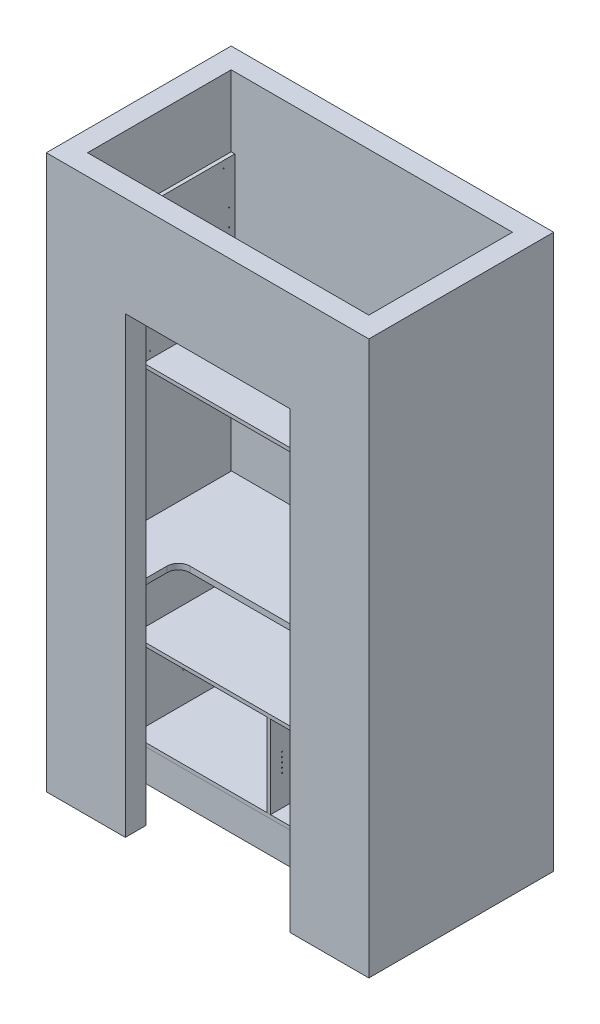
SolidWorks part; units mm, degrees
ref_plane "Front" through (0, 0, 0) normal (0, 0, 1) x (1, 0, 0)
ref_plane "Top" through (0, 0, 0) normal (0, 1, 0) x (1, 0, 0)
ref_plane "Right" through (0, 0, 0) normal (1, 0, 0) x (0, 0, -1)
sketch "Sketch1" plane through (0, 0, 0) normal (0, 1, 0) x (1, 0, 0)
  line L0 (-90, 90) -> (1318, 90)
  line L1 (0, 0) -> (1228, 0)
  line L2 (0, 0) -> (0, -627)
  line L3 (0, -627) -> (255, -627)
  line L4 (1228, 0) -> (1228, -627)
  line L5 (1318, 90) -> (1318, -717)
  line L6 (-90, -717) -> (255, -717)
  line L7 (-90, 90) -> (-90, -717)
  line L8 (255, -627) -> (255, -717)
  line L9 (973, -627) -> (973, -717)
  line L10 (973, -717) -> (1318, -717)
  line L11 (973, -627) -> (1228, -627)
  line L12 (-90, -717) -> (1318, -717) construction
  line L13 (255, -627) -> (973, -627)
  line L14 (0, -627) -> (1228, -627) construction
  line L15 (255, -717) -> (973, -717)
  dimension "D1" = 1228
  dimension "D2" = 627
  dimension "D4" = 255
  dimension "D5" = 255
  dimension "D3" = 90
extrude "Boss-Extrude1" add sketch "Sketch1" along normal blind 2416 contours L11 L9 L10 L5 L0 L7 L6 L8 L3 L2 L1 L4 | L8 L15 L9 L13 region at (614, 0, -73.7713) region at (614, 0, 672)
sketch "Sketch2" plane through (0, 0, 717) normal (0, 0, 1) x (1, 0, 0)
  line L0 (-90, 0) -> (1318, 0) construction
  line L1 (255, 0) -> (973, 0)
  line L2 (255, 0) -> (255, 1980)
  line L3 (255, 1980) -> (973, 1980)
  line L4 (973, 0) -> (973, 1980)
  line L5 (0, 2416) -> (0, 0) construction
  line L6 (1228, 2416) -> (1228, 0) construction
  dimension "D1" = 255
  dimension "D2" = 255
  dimension "D3" = 1980
  dimension "D4" = 718
extrude "Cut-Extrude1" cut sketch "Sketch2" against normal blind 100
sketch "Sketch4" plane through (0, 0, 0) normal (0, 0, 1) x (1, 0, 0)
  line L0 (1228, 2416) -> (1228, 0) construction
  line L5 (0, 120) -> (1228, 120)
  line L7 (16, 136) -> (1212, 136)
  line L9 (16, 513.5) -> (606, 513.5)
  line L11 (16, 497.5) -> (606, 497.5)
  line L13 (16, 875) -> (1212, 875)
  line L15 (16, 900) -> (1212, 900)
  line L21 (16, 1500) -> (1212, 1500)
  line L23 (16, 1516) -> (1212, 1516)
  line L25 (16, 1766) -> (1212, 1766)
  line L27 (16, 1782) -> (1212, 1782)
  line L37 (622, 513.5) -> (1212, 513.5)
  line L38 (622, 497.5) -> (1212, 497.5)
  line L39 (16, 1500) -> (0, 1500)
  line L40 (0, 120) -> (16, 120)
  line L41 (0, 120) -> (0, 2320)
  line L42 (598, 120) -> (614, 120)
  line L43 (606, 136) -> (606, 875)
  line L44 (606, 875) -> (614, 875)
  line L46 (614, 875) -> (622, 875)
  line L48 (614, 120) -> (630, 120)
  line L49 (622, 875) -> (622, 136)
  line L50 (0, 2320) -> (16, 2320)
  line L51 (16, 120) -> (16, 2320)
  line L52 (1212, 1500) -> (1228, 1500)
  line L54 (1228, 2320) -> (1228, 120)
  line L56 (1212, 2320) -> (1212, 120)
  line L57 (614, 136) -> (614, 171.2625) construction
  line L58 (1212, 2320) -> (1228, 2320)
  line L59 (-90, 0) -> (255, 0) construction
  line L60 (311, 513.5) -> (311, 875) construction
  line L61 (311, 497.5) -> (311, 136) construction
  dimension "D2" = 120
  dimension "D4" = 16
  dimension "D5" = 16
  dimension "D6" = 8
  dimension "D3" = 25
  dimension "D7" = 1500
  dimension "D8" = 250
  dimension "D9" = 16
  dimension "D10" = 2200
  dimension "D11" = 16
  dimension "D12" = 16
  dimension "D13" = 16
  dimension "D14" = 16
  dimension "D15" = 900
sketch "Sketch6" plane through (0, 0, 0) normal (0, 0, 1) x (1, 0, 0)
  line L0 (0, 120) -> (0, 2320) construction
  line L13 (16, 875) -> (0, 875)
  line L14 (16, 875) -> (16, 136)
  line L15 (16, 136) -> (0, 136)
  line L16 (0, 875) -> (0, 136)
  line L17 (16, 136) -> (1212, 136) construction
  line L18 (1228, 2320) -> (1228, 120) construction
  line L19 (1212, 875) -> (1228, 875)
  line L20 (1212, 875) -> (1212, 136)
  line L21 (1212, 136) -> (1228, 136)
  line L22 (1228, 875) -> (1228, 136)
  line L24 (606, 497.5) -> (622, 497.5)
  line L25 (606, 497.5) -> (606, 136)
  line L26 (606, 136) -> (622, 136)
  line L27 (622, 497.5) -> (622, 136)
extrude "Boss-Extrude2" add sketch "Sketch6" along normal blind 450 separate body
sketch "Sketch7" plane through (0, 0, 0) normal (0, 0, 1) x (1, 0, 0)
  line L0 (1228, 2320) -> (1228, 120) construction
  line L1 (0, 120) -> (1228, 120)
  line L2 (0, 120) -> (0, 136)
  line L3 (0, 136) -> (1228, 136)
  line L4 (1228, 120) -> (1228, 136)
  line L6 (16, 497.5) -> (16, 513.5)
  line L7 (16, 513.5) -> (1212, 513.5)
  line L9 (16, 497.5) -> (1212, 497.5)
  line L12 (1212, 497.5) -> (1212, 513.5)
  line L13 (0, 875) -> (1228, 875)
  line L14 (0, 875) -> (0, 900)
  line L15 (0, 900) -> (1228, 900)
  line L16 (1228, 875) -> (1228, 900)
  line L17 (16, 900) -> (1212, 900) construction
  line L19 (1212, 2320) -> (1212, 120) construction
  line L20 (16, 120) -> (16, 2320) construction
extrude "Boss-Extrude3" add sketch "Sketch7" along normal blind 450 separate body
sketch "Sketch8" plane through (0, 0, 0) normal (0, 0, 1) x (1, 0, 0)
  line L0 (0, 120) -> (0, 2320) construction
  line L1 (16, 1516) -> (0, 1516)
  line L2 (16, 1516) -> (16, 2106)
  line L3 (16, 2106) -> (0, 2106)
  line L4 (0, 1516) -> (0, 2106)
  line L5 (1228, 2320) -> (1228, 120) construction
  line L6 (1212, 1516) -> (1228, 1516)
  line L7 (1212, 1516) -> (1212, 2106)
  line L8 (1212, 2106) -> (1228, 2106)
  line L9 (1228, 1516) -> (1228, 2106)
  line L10 (16, 120) -> (16, 2320) construction
  dimension "D1" = 590
extrude "Boss-Extrude4" add sketch "Sketch8" along normal blind 400 separate body
sketch "Sketch9" plane through (0, 0, 0) normal (0, 0, 1) x (1, 0, 0)
  line L0 (1227, 1516) -> (1227, 1500)
  line L1 (16, 1782) -> (1212, 1782)
  line L2 (16, 1782) -> (16, 1766)
  line L3 (16, 1766) -> (1212, 1766)
  line L4 (1212, 1782) -> (1212, 1766)
  line L5 (1, 1516) -> (1227, 1516)
  line L6 (0, 1516) -> (0, 1500) construction
  line L7 (1, 1500) -> (1227, 1500)
  line L8 (1228, 1516) -> (1228, 1500) construction
  line L9 (1, 1516) -> (1, 1500)
  dimension "D1" = 1
  dimension "D2" = 1
extrude "Boss-Extrude5" add sketch "Sketch9" along normal blind 400 separate body
sketch "Sketch11" plane through (0, 900, 0) normal (0, 1, 0) x (1, 0, 0)
  line L0 (0, -450) -> (0, -627)
  line L1 (0, -627) -> (220, -627)
  line L2 (0, -627) -> (1228, -627) construction
  line L3 (220, -627) -> (220, -450)
  line L4 (1228, -450) -> (0, -450) construction
  line L5 (614, 90) -> (614, 254.9806) construction
  line L6 (-90, 90) -> (1318, 90) construction
  line L7 (0, -450) -> (220, -450)
  line L8 (1228, -450) -> (1008, -450)
  line L9 (1008, -627) -> (1008, -450)
  line L10 (1228, -627) -> (1008, -627)
  line L11 (1228, -450) -> (1228, -627)
  dimension "D1" = 220
extrude "Boss-Extrude6" add sketch "Sketch11" against normal up to surface (25 mm away) up to face at (614, 875, 225)
fillet "Fillet1" radius 50 2 edges at (220, 887.5, 450) (1008, 887.5, 450)
sketch "Sketch18" plane through (0, 120, 0) normal (0, -1, 0) x (1, 0, 0)
  line L0 (16, 0) -> (1212, 0) construction
  line L1 (0, 627) -> (1.5, 627)
  line L2 (0, 627) -> (0, 0)
  line L3 (0, 0) -> (1.5, 0)
  line L4 (1.5, 627) -> (1.5, 0)
  line L5 (1.5, 73.7952) -> (1226.5, 73.7952) construction
  line L6 (1228, 627) -> (1226.5, 627)
  line L7 (1228, 627) -> (1228, 0)
  line L8 (1228, 0) -> (1226.5, 0)
  line L9 (1226.5, 627) -> (1226.5, 0)
  line L10 (614, 73.7952) -> (614, -90) construction
  line L11 (-90, -90) -> (1318, -90) construction
  dimension "D1" = 1225
extrude "Cut-Extrude5" cut sketch "Sketch18" against normal through all
hole_wizard "Ø2.0 (2) Diameter Hole1" positions "Sketch20" profile "Sketch21" hole size "Ø2.0" standard "ISO"
sketch "Sketch20" plane through (0, 120, 0) normal (0, -1, 0) x (-1, 0, 0)
  line L1 (-646, -32) -> (-582, -32)
  line L2 (-646, -32) -> (-646, -96)
  line L3 (-646, -96) -> (-582, -96)
  line L4 (-582, -32) -> (-582, -96)
  line L7 (-614, -32) -> (-614, 0) construction
  line L8 (-1.5, 0) -> (-1226.5, 0) construction
  line L10 (0, 0) -> (-1228, 0) construction
  line L12 (-1176.5, -336.5) -> (-1112.5, -336.5)
  line L13 (-1176.5, -336.5) -> (-1176.5, -400.5)
  line L14 (-1176.5, -400.5) -> (-1112.5, -400.5)
  line L15 (-1112.5, -336.5) -> (-1112.5, -400.5)
  line L17 (-646, -336.5) -> (-582, -336.5)
  line L18 (-646, -336.5) -> (-646, -400.5)
  line L19 (-646, -400.5) -> (-582, -400.5)
  line L20 (-582, -336.5) -> (-582, -400.5)
  line L22 (-115.5, -336.5) -> (-51.5, -336.5)
  line L23 (-115.5, -336.5) -> (-115.5, -400.5)
  line L24 (-115.5, -400.5) -> (-51.5, -400.5)
  line L25 (-51.5, -336.5) -> (-51.5, -400.5)
  line L26 (-1226.5, -450) -> (-1226.5, 0) construction
  line L27 (-1.5, 0) -> (-1.5, -450) construction
  line L28 (-270, -450) -> (-958, -450) construction
  point P0 (-646, -32)
  point P2 (-582, -32)
  point P4 (-582, -96)
  point P6 (-646, -96)
  point P82 (-646, -400.5)
  point P84 (-646, -336.5)
  point P86 (-582, -336.5)
  point P88 (-582, -400.5)
  point P90 (-51.5, -400.5)
  point P92 (-51.5, -336.5)
  point P94 (-115.5, -336.5)
  point P96 (-115.5, -400.5)
  point P98 (-1176.5, -336.5)
  point P100 (-1112.5, -336.5)
  point P102 (-1112.5, -400.5)
  point P104 (-1176.5, -400.5)
  dimension "D1" = 50
  dimension "D2" = 64
  dimension "D3" = 50
  dimension "D4" = 49.5
  dimension "D5" = 64
  dimension "D6" = 32
sketch "Sketch21" plane through (646, 120, 32) normal (1, 0, 0) x (0, 0, -1)
  line L0 (0, 0) -> (0, 10.6009)
  line L1 (0, 10.6009) -> (1, 10)
  line L2 (1, 10) -> (1, 0)
  line L5 (1, 0) -> (0, 0)
  line L10 (0, 10.6009) -> (-1, 10) construction
  line L11 (0, -6.35) -> (0, 107.95) construction
  dimension "Hole Dia." = 2
  dimension "Hole Depth" = 10
  dimension "Drill Angle" = 118
hole_wizard "Ø2.0 (2) Diameter Hole2" positions "Sketch22" profile "Sketch23" hole size "Ø2.0" standard "ISO"
sketch "Sketch22" plane through (0, 120, 0) normal (0, -1, 0) x (-1, 0, 0)
  line L0 (-1220, -15) -> (-1220, -435) construction
  line L2 (-1228, 0) -> (-1228, -627) construction
  line L3 (0, 0) -> (0, -627) construction
  line L4 (-1.5, -450) -> (-1226.5, -450) construction
  line L5 (0, 0) -> (-1228, 0) construction
  line L6 (-614, -435) -> (-614, -450) construction
  line L7 (-270, -450) -> (-958, -450) construction
  point P0 (-1220, -435)
  point P2 (-1220, -225)
  point P4 (-1220, -15)
  point P6 (-614, -15)
  point P8 (-614, -225)
  point P10 (-614, -435)
  point P12 (-8, -15)
  point P14 (-8, -225)
  point P16 (-8, -435)
  dimension "D1" = 8
  dimension "D2" = 8
  dimension "D3" = 15
  dimension "D4" = 15
sketch "Sketch23" plane through (1220, 120, 435) normal (1, 0, 0) x (0, 0, -1)
  line L0 (0, 0) -> (0, 10.6009)
  line L1 (0, 10.6009) -> (1, 10)
  line L2 (1, 10) -> (1, 0)
  line L5 (1, 0) -> (0, 0)
  line L10 (0, 10.6009) -> (-1, 10) construction
  line L11 (0, -6.35) -> (0, 107.95) construction
  dimension "Hole Dia." = 2
  dimension "Hole Depth" = 10
  dimension "Drill Angle" = 118
sketch "Sketch24" plane through (0, 120, 0) normal (0, -1, 0) x (1, 0, 0)
  circle A0 centre (8, 435) radius 2.5
  circle A1 centre (8, 225) radius 2.5
  circle A2 centre (8, 15) radius 2.5
  circle A3 centre (614, 435) radius 2.5
  circle A4 centre (614, 225) radius 2.5
  circle A5 centre (614, 15) radius 2.5
  circle A6 centre (1220, 15) radius 2.5
  circle A7 centre (1220, 225) radius 2.5
  circle A8 centre (1220, 435) radius 2.5
  dimension "D1" = 5
extrude "Cut-Extrude6" cut sketch "Sketch24" against normal blind 1
sketch "Sketch25" plane through (16, 0, 0) normal (1, 0, 0) x (0, 0, -1)
  line L0 (-450, 497.5) -> (0, 497.5) construction
  line L1 (-450, 497.5) -> (0, 497.5) construction
  line L2 (-400, 497.5) -> (-50, 497.5) construction
  circle A0 centre (-400, 497.5) radius 2.5
  circle A1 centre (-50, 497.5) radius 2.5
  circle A2 centre (-225, 497.5) radius 2.5
  dimension "D1" = 5
  dimension "D2" = 350
extrude "Cut-Extrude7" cut sketch "Sketch25" against normal through all both and the other way through all
sketch "Sketch26" plane through (16, 0, 0) normal (1, 0, 0) x (0, 0, -1)
  line L0 (-400, 497.5) -> (-50, 497.5) construction
  circle A0 centre (-400, 308.75) radius 2.5
  circle A1 centre (-225, 308.75) radius 2.5
  circle A2 centre (-50, 308.75) radius 2.5
  circle A3 centre (-400, 497.5) radius 2.5 construction
  circle A4 centre (-400, 328.75) radius 2.5
  circle A5 centre (-225, 328.75) radius 2.5
  circle A6 centre (-50, 328.75) radius 2.5
  circle A7 centre (-400, 348.75) radius 2.5
  circle A8 centre (-225, 348.75) radius 2.5
  circle A9 centre (-50, 348.75) radius 2.5
  circle A10 centre (-400, 288.75) radius 2.5
  circle A11 centre (-225, 288.75) radius 2.5
  circle A12 centre (-50, 288.75) radius 2.5
  circle A13 centre (-400, 268.75) radius 2.5
  circle A14 centre (-225, 268.75) radius 2.5
  circle A15 centre (-50, 268.75) radius 2.5
  dimension "D1" = 188.75
  dimension "D2" = 3
  dimension "D3" = 3
extrude "Cut-Extrude8" cut sketch "Sketch26" against normal through all both and the other way through all
sketch "Sketch34" plane through (0, 497.5, 0) normal (0, -1, 0) x (1, 0, 0)
  line L0 (16, 450) -> (16, 0) construction
  line L1 (16, 403) -> (39.9125, 403)
  line L2 (16, 403) -> (16, 397)
  line L3 (16, 397) -> (39.9125, 397)
  line L4 (41.5, 401.4125) -> (41.5, 398.5875)
  line L15 (16, 400) -> (41.5, 400) construction
  line L16 (1.5, 0) -> (1.5, 450) construction
  line L17 (0, 400) -> (16, 400) construction
  line L18 (16, 228) -> (39.9125, 228)
  line L19 (16, 228) -> (16, 222)
  line L20 (16, 222) -> (39.9125, 222)
  line L21 (41.5, 226.4125) -> (41.5, 223.5875)
  line L22 (16, 225) -> (41.5, 225) construction
  line L23 (16, 53) -> (39.9125, 53)
  line L24 (16, 53) -> (16, 47)
  line L25 (16, 47) -> (39.9125, 47)
  line L26 (41.5, 51.4125) -> (41.5, 48.5875)
  line L27 (16, 50) -> (41.5, 50) construction
  line L28 (614, 435) -> (614, 225) construction
  line L29 (1212, 50) -> (1186.5, 50) construction
  line L30 (1212, 225) -> (1186.5, 225) construction
  line L31 (1212, 400) -> (1186.5, 400) construction
  line L32 (1186.5, 51.4125) -> (1186.5, 48.5875)
  line L33 (1212, 47) -> (1188.0875, 47)
  line L34 (1212, 53) -> (1212, 47)
  line L35 (1212, 53) -> (1188.0875, 53)
  line L36 (1186.5, 226.4125) -> (1186.5, 223.5875)
  line L37 (1212, 222) -> (1188.0875, 222)
  line L38 (1212, 228) -> (1212, 222)
  line L39 (1212, 228) -> (1188.0875, 228)
  line L40 (1186.5, 401.4125) -> (1186.5, 398.5875)
  line L41 (1212, 397) -> (1188.0875, 397)
  line L42 (1212, 403) -> (1212, 397)
  line L43 (1212, 403) -> (1188.0875, 403)
  arc A0 (39.9125, 397) -> (41.5, 398.5875) centre (39.9125, 398.5875) ccw
  arc A1 (39.9125, 403) -> (41.5, 401.4125) centre (39.9125, 401.4125) cw
  arc A2 (39.9125, 222) -> (41.5, 223.5875) centre (39.9125, 223.5875) ccw
  arc A3 (39.9125, 228) -> (41.5, 226.4125) centre (39.9125, 226.4125) cw
  arc A4 (39.9125, 47) -> (41.5, 48.5875) centre (39.9125, 48.5875) ccw
  arc A5 (39.9125, 53) -> (41.5, 51.4125) centre (39.9125, 51.4125) cw
  arc A6 (1188.0875, 53) -> (1186.5, 51.4125) centre (1188.0875, 51.4125) ccw
  arc A7 (1188.0875, 47) -> (1186.5, 48.5875) centre (1188.0875, 48.5875) cw
  arc A8 (1188.0875, 228) -> (1186.5, 226.4125) centre (1188.0875, 226.4125) ccw
  arc A9 (1188.0875, 222) -> (1186.5, 223.5875) centre (1188.0875, 223.5875) cw
  arc A10 (1188.0875, 403) -> (1186.5, 401.4125) centre (1188.0875, 401.4125) ccw
  arc A11 (1188.0875, 397) -> (1186.5, 398.5875) centre (1188.0875, 398.5875) cw
  point P26 (41.5, 397)
  point P29 (41.5, 403)
  point P73 (1186.5, 403)
  point P74 (1186.5, 397)
  dimension "D3" = 1.5875
  dimension "D1" = 40
  dimension "D2" = 6
  dimension "D4" = 3
extrude "Cut-Extrude9" cut sketch "Sketch34" against normal blind 3
hole_wizard "Ø2.0 (2) Diameter Hole3" positions "Sketch35" profile "Sketch36" hole size "Ø2.0" standard "ISO"
sketch "Sketch35" plane through (622, 0, 0) normal (1, 0, 0) x (0, 0, -1)
  line L0 (-450, 136) -> (-450, 497.5) construction
  line L1 (-450, 497.5) -> (0, 497.5) construction
  line L2 (0, 875) -> (0, 136) construction
  point P0 (-400, 481.5)
  point P7 (-100, 481.5)
  dimension "D1" = 50
  dimension "D2" = 16
  dimension "D3" = 100
sketch "Sketch36" plane through (622, 481.5, 400) normal (0, 1, 0) x (0, 0, -1)
  line L0 (0, 0) -> (0, 18.6009)
  line L1 (0, 18.6009) -> (1, 18)
  line L2 (1, 18) -> (1, 0)
  line L5 (1, 0) -> (0, 0)
  line L10 (0, 18.6009) -> (-1, 18) construction
  line L11 (0, -6.35) -> (0, 107.95) construction
  dimension "Hole Dia." = 2
  dimension "Hole Depth" = 18
  dimension "Drill Angle" = 118
hole_wizard "Ø2.0 (2) Diameter Hole4" positions "Sketch37" profile "Sketch38" hole size "Ø2.0" standard "ISO" end condition through all
sketch "Sketch37" plane through (1318, 0, 0) normal (1, 0, 0) x (0, 0, -1)
  line L0 (-450, 136) -> (-450, 875) construction
  line L1 (0, 120) -> (0, 2320) construction
  line L2 (-450, 875) -> (0, 875) construction
  line L3 (-450, 136) -> (0, 136) construction
  point P0 (-425, 171)
  point P2 (-425, 471)
  point P4 (-425, 825)
  point P6 (-50, 825)
  point P10 (-50, 171)
  dimension "D1" = 25
  dimension "D2" = 50
  dimension "D3" = 50
  dimension "D4" = 35
  dimension "D5" = 300
sketch "Sketch38" plane through (1318, 171, 425) normal (0, 1, 0) x (0, 0, -1)
  line L0 (0, 0) -> (0, 1408)
  line L1 (0, 1408) -> (1, 1408)
  line L2 (1, 1408) -> (1, 0)
  line L5 (1, 0) -> (0, 0)
  line L11 (0, -6.35) -> (0, 107.95) construction
  dimension "Thru Hole Dia." = 2
  dimension "Thru Hole Depth" = 1408
sketch "Sketch39" plane through (16, 0, 0) normal (1, 0, 0) x (0, 0, -1)
  circle A0 centre (-425, 171) radius 2.5
  circle A1 centre (-50, 171) radius 2.5
  circle A2 centre (-425, 471) radius 2.5
  circle A3 centre (-425, 825) radius 2.5
  circle A4 centre (-50, 825) radius 2.5
  dimension "D1" = 5
extrude "Cut-Extrude10" cut sketch "Sketch39" against normal blind 1
sketch "Sketch40" plane through (1212, 0, 0) normal (-1, 0, 0) x (0, 0, 1)
  circle A1 centre (50, 825) radius 2.5
  circle A2 centre (50, 825) radius 2.5
  circle A3 centre (425, 825) radius 2.5
  circle A4 centre (425, 825) radius 2.5
  circle A5 centre (425, 471) radius 2.5
  circle A6 centre (425, 471) radius 2.5
  circle A7 centre (50, 171) radius 2.5
  circle A8 centre (50, 171) radius 2.5
  circle A9 centre (425, 171) radius 2.5
  circle A10 centre (425, 171) radius 2.5
  dimension "D1" = 0
  dimension "D2" = 0
  dimension "D3" = 0
  dimension "D4" = 0
  dimension "D5" = 0
extrude "Cut-Extrude11" cut sketch "Sketch40" against normal blind 1
sketch "Sketch41" plane through (0, 1782, 0) normal (0, 1, 0) x (1, 0, 0)
  line L0 (1212, -400) -> (16, -400) construction
  line L1 (16, 0) -> (17, 0)
  line L2 (16, 0) -> (16, -400)
  line L3 (16, -400) -> (17, -400)
  line L4 (17, 0) -> (17, -400)
  line L6 (1212, 0) -> (1211, 0)
  line L7 (1212, 0) -> (1212, -400)
  line L8 (1212, -400) -> (1211, -400)
  line L9 (1211, 0) -> (1211, -400)
  dimension "D1" = 1
  dimension "D2" = 1
extrude "Cut-Extrude12" cut sketch "Sketch41" against normal up to next (16 mm away)
hole_wizard "Ø2.0 (2) Diameter Hole5" positions "Sketch42" profile "Sketch43" hole size "Ø2.0" standard "ISO" end condition through all
sketch "Sketch42" plane through (0, 1500, 0) normal (0, -1, 0) x (-1, 0, 0)
  line L0 (-1228, -400) -> (-1228, 0) construction
  line L1 (0, -400) -> (0, 0) construction
  line L2 (-1, -400) -> (-1227, -400) construction
  line L3 (0, 0) -> (-16, 0) construction
  point P0 (-1220, -380)
  point P2 (-1220, -200)
  point P4 (-1220, -20)
  point P6 (-8, -380)
  point P8 (-8, -200)
  point P10 (-8, -20)
  dimension "D1" = 8
  dimension "D2" = 8
  dimension "D3" = 20
  dimension "D4" = 20
  dimension "D5" = 180
sketch "Sketch43" plane through (1220, 1500, 380) normal (1, 0, 0) x (0, 0, -1)
  line L0 (0, 0) -> (0, 916)
  line L1 (0, 916) -> (1, 916)
  line L2 (1, 916) -> (1, 0)
  line L5 (1, 0) -> (0, 0)
  line L11 (0, -6.35) -> (0, 107.95) construction
  dimension "Thru Hole Dia." = 2
  dimension "Thru Hole Depth" = 916
sketch "Sketch44" plane through (0, 1500, 0) normal (0, -1, 0) x (1, 0, 0)
  circle A0 centre (8, 380) radius 2.5
  circle A1 centre (8, 200) radius 2.5
  circle A2 centre (8, 20) radius 2.5
  circle A3 centre (1220, 20) radius 2.5
  circle A4 centre (1220, 200) radius 2.5
  circle A5 centre (1220, 380) radius 2.5
  dimension "D1" = 5
extrude "Cut-Extrude13" cut sketch "Sketch44" against normal blind 1
hole_wizard "Ø5.0 (5) Diameter Hole1" positions "Sketch45" profile "Sketch46" hole size "Ø5.0" standard "ISO" end condition through all
sketch "Sketch45" plane through (1228, 0, 0) normal (1, 0, 0) x (0, 0, -1)
  line L0 (-400, 1766) -> (0, 1766) construction
  line L1 (-400, 1516) -> (-400, 2106) construction
  line L2 (0, 120) -> (0, 2320) construction
  point P0 (-375, 1766)
  point P4 (-200, 1766)
  point P6 (-25, 1766)
  point P8 (-375, 1841)
  point P10 (-200, 1841)
  point P12 (-25, 1841)
  point P14 (-375, 1916)
  point P16 (-200, 1916)
  point P18 (-25, 1916)
  dimension "D1" = 25
  dimension "D2" = 25
  dimension "D3" = 75
  dimension "D4" = 75
sketch "Sketch46" plane through (1228, 1766, 375) normal (0, 1, 0) x (0, 0, -1)
  line L0 (0, 0) -> (0, 1318)
  line L1 (0, 1318) -> (2.5, 1318)
  line L2 (2.5, 1318) -> (2.5, 0)
  line L5 (2.5, 0) -> (0, 0)
  line L11 (0, -6.35) -> (0, 107.95) construction
  dimension "Thru Hole Dia." = 5
  dimension "Thru Hole Depth" = 1318
hole_wizard "Ø2.0 (2) Diameter Hole6" positions "Sketch48" profile "Sketch49" hole size "Ø2.0" standard "ISO" end condition through all
sketch "Sketch48" plane through (1228, 0, 0) normal (1, 0, 0) x (0, 0, -1)
  line L0 (-400, 1516) -> (0, 1516) construction
  line L1 (-400, 1516) -> (-400, 2106) construction
  line L2 (0, 120) -> (0, 2320) construction
  line L3 (-400, 2106) -> (0, 2106) construction
  circle A0 centre (-375, 1766) radius 2.5 construction
  point P0 (-370, 1546)
  point P2 (-370, 2076)
  point P4 (-370, 1801)
  point P6 (-50, 1546)
  point P8 (-50, 1801)
  point P10 (-50, 2076)
  dimension "D1" = 30
  dimension "D2" = 30
  dimension "D3" = 50
  dimension "D4" = 35
  dimension "D5" = 30
sketch "Sketch49" plane through (1228, 1546, 370) normal (0, 1, 0) x (0, 0, -1)
  line L0 (0, 0) -> (0, 1318)
  line L1 (0, 1318) -> (1, 1318)
  line L2 (1, 1318) -> (1, 0)
  line L5 (1, 0) -> (0, 0)
  line L11 (0, -6.35) -> (0, 107.95) construction
  dimension "Thru Hole Dia." = 2
  dimension "Thru Hole Depth" = 1318
sketch "Sketch50" plane through (16, 0, 0) normal (1, 0, 0) x (0, 0, -1)
  circle A0 centre (-370, 2076) radius 2.5
  circle A1 centre (-50, 2076) radius 2.5
  circle A2 centre (-50, 1801) radius 2.5
  circle A3 centre (-370, 1801) radius 2.5
  circle A4 centre (-370, 1546) radius 2.5
  circle A5 centre (-50, 1546) radius 2.5
  dimension "D1" = 5
extrude "Cut-Extrude14" cut sketch "Sketch50" against normal blind 1
sketch "Sketch51" plane through (1212, 0, 0) normal (-1, 0, 0) x (0, 0, 1)
  circle A1 centre (370, 1546) radius 2.5
  circle A2 centre (370, 1546) radius 2.5
  circle A3 centre (370, 1801) radius 2.5
  circle A4 centre (370, 1801) radius 2.5
  circle A5 centre (50, 1801) radius 2.5
  circle A6 centre (50, 1801) radius 2.5
  circle A7 centre (50, 2076) radius 2.5
  circle A8 centre (50, 2076) radius 2.5
  circle A9 centre (370, 2076) radius 2.5
  circle A10 centre (370, 2076) radius 2.5
  circle A11 centre (50, 1546) radius 2.5
  circle A12 centre (50, 1546) radius 2.5
  dimension "D1" = 0
  dimension "D2" = 0
  dimension "D3" = 0
  dimension "D4" = 0
  dimension "D5" = 0
  dimension "D6" = 0
extrude "Cut-Extrude15" cut sketch "Sketch51" against normal blind 1
sketch "Sketch52" plane through (0, 1766, 0) normal (0, -1, 0) x (1, 0, 0)
  line L0 (17, 0) -> (17, 400) construction
  line L1 (17, 378) -> (38.4125, 378)
  line L2 (17, 378) -> (17, 372)
  line L3 (17, 372) -> (38.4125, 372)
  line L4 (40, 376.4125) -> (40, 373.5875)
  line L5 (17, 375) -> (40, 375) construction
  line L6 (0, 400) -> (0, 0) construction
  line L7 (17, 400) -> (1211, 400) construction
  line L9 (614, 435) -> (614, -96.6075) construction
  line L13 (17, 203) -> (38.4125, 203)
  line L18 (17, 203) -> (17, 197)
  line L19 (17, 197) -> (38.4125, 197)
  line L20 (40, 201.4125) -> (40, 198.5875)
  line L21 (17, 200) -> (40, 200) construction
  line L22 (17, 28) -> (38.4125, 28)
  line L23 (17, 28) -> (17, 22)
  line L24 (17, 22) -> (38.4125, 22)
  line L25 (40, 26.4125) -> (40, 23.5875)
  line L26 (17, 25) -> (40, 25) construction
  line L27 (1211, 25) -> (1188, 25) construction
  line L28 (1211, 200) -> (1188, 200) construction
  line L29 (1211, 375) -> (1188, 375) construction
  line L30 (1188, 26.4125) -> (1188, 23.5875)
  line L31 (1211, 22) -> (1189.5875, 22)
  line L32 (1211, 28) -> (1211, 22)
  line L33 (1211, 28) -> (1189.5875, 28)
  line L34 (1188, 201.4125) -> (1188, 198.5875)
  line L35 (1211, 197) -> (1189.5875, 197)
  line L36 (1211, 203) -> (1211, 197)
  line L37 (1211, 203) -> (1189.5875, 203)
  line L38 (1188, 376.4125) -> (1188, 373.5875)
  line L39 (1211, 372) -> (1189.5875, 372)
  line L40 (1211, 378) -> (1211, 372)
  line L41 (1211, 378) -> (1189.5875, 378)
  arc A0 (38.4125, 372) -> (40, 373.5875) centre (38.4125, 373.5875) ccw
  arc A1 (38.4125, 378) -> (40, 376.4125) centre (38.4125, 376.4125) cw
  arc A6 (38.4125, 197) -> (40, 198.5875) centre (38.4125, 198.5875) ccw
  arc A7 (38.4125, 203) -> (40, 201.4125) centre (38.4125, 201.4125) cw
  arc A8 (38.4125, 22) -> (40, 23.5875) centre (38.4125, 23.5875) ccw
  arc A9 (38.4125, 28) -> (40, 26.4125) centre (38.4125, 26.4125) cw
  arc A10 (1189.5875, 28) -> (1188, 26.4125) centre (1189.5875, 26.4125) ccw
  arc A11 (1189.5875, 22) -> (1188, 23.5875) centre (1189.5875, 23.5875) cw
  arc A12 (1189.5875, 203) -> (1188, 201.4125) centre (1189.5875, 201.4125) ccw
  arc A13 (1189.5875, 197) -> (1188, 198.5875) centre (1189.5875, 198.5875) cw
  arc A14 (1189.5875, 378) -> (1188, 376.4125) centre (1189.5875, 376.4125) ccw
  arc A15 (1189.5875, 372) -> (1188, 373.5875) centre (1189.5875, 373.5875) cw
  dimension "D1" = 1.5875
  dimension "D2" = 6
  dimension "D3" = 40
  dimension "D4" = 25
  dimension "D5" = 3
extrude "Cut-Extrude16" cut sketch "Sketch52" against normal blind 3
sketch "Sketch54" plane through (0, 0, 450) normal (0, 0, 1) x (1, 0, 0)
  line L0 (1226.5, 120) -> (1226.5, 136) construction
  line L1 (1.5, 120) -> (1226.5, 120)
  line L2 (1.5, 120) -> (1.5, -19)
  line L3 (1.5, -19) -> (1226.5, -19)
  line L4 (1226.5, 120) -> (1226.5, -19)
  dimension "D1" = 139
extrude "Boss-Extrude7" add sketch "Sketch54" against normal blind 16 separate body
sketch "Sketch55" plane through (0, 0, 434) normal (0, 0, -1) x (-1, 0, 0)
  line L0 (-1226.5, 120) -> (-1.5, 120) construction
  line L1 (-1169.5, 80) -> (-1119.5, 80)
  line L3 (-1169.5, 77) -> (-1119.5, 77)
  line L5 (-108.5, 80) -> (-58.5, 80)
  line L7 (-108.5, 77) -> (-58.5, 77)
  line L8 (-1144.5, 80) -> (-1144.5, -56.6281) construction
  line L9 (-1226.5, -19) -> (-1226.5, 120) construction
  line L10 (-83.5, 80) -> (-83.5, 123.5184) construction
  line L11 (-1.5, 120) -> (-1.5, -19) construction
  arc A0 (-1169.5, 80) -> (-1169.5, 77) centre (-1169.5, 78.5) ccw
  arc A1 (-1119.5, 77) -> (-1119.5, 80) centre (-1119.5, 78.5) ccw
  arc A2 (-108.5, 80) -> (-108.5, 77) centre (-108.5, 78.5) ccw
  arc A3 (-58.5, 77) -> (-58.5, 80) centre (-58.5, 78.5) ccw
  dimension "D1" = 3
  dimension "D2" = 50
  dimension "D3" = 40
  dimension "D4" = 3
  dimension "D5" = 82
  dimension "D6" = 82
extrude "Cut-Extrude17" cut sketch "Sketch55" against normal blind 8
delete or keep bodies "Body-Delete/Keep 1" [suppressed] type delete bodies bodies 102
delete or keep bodies "Body-Delete/Keep 2" [suppressed] type keep bodies bodies 124
delete or keep bodies "Body-Delete/Keep 3" [suppressed] type keep bodies bodies 127
delete or keep bodies "Body-Delete/Keep 4" [suppressed] type keep bodies bodies 147
delete or keep bodies "Body-Delete/Keep 5" [suppressed] type keep bodies bodies 148
delete or keep bodies "Body-Delete/Keep 6" [suppressed] type keep bodies bodies 151
delete or keep bodies "Body-Delete/Keep 7" [suppressed] type keep bodies bodies 152
delete or keep bodies "Body-Delete/Keep 8" [suppressed] type keep bodies bodies 157
delete or keep bodies "Body-Delete/Keep 9" [suppressed] type keep bodies bodies 163
delete or keep bodies "Body-Delete/Keep 10" [suppressed] type keep bodies bodies 164
delete or keep bodies "Body-Delete/Keep 11" [suppressed] type keep bodies bodies 165
delete or keep bodies "Body-Delete/Keep 12" [suppressed] type keep bodies bodies 167
